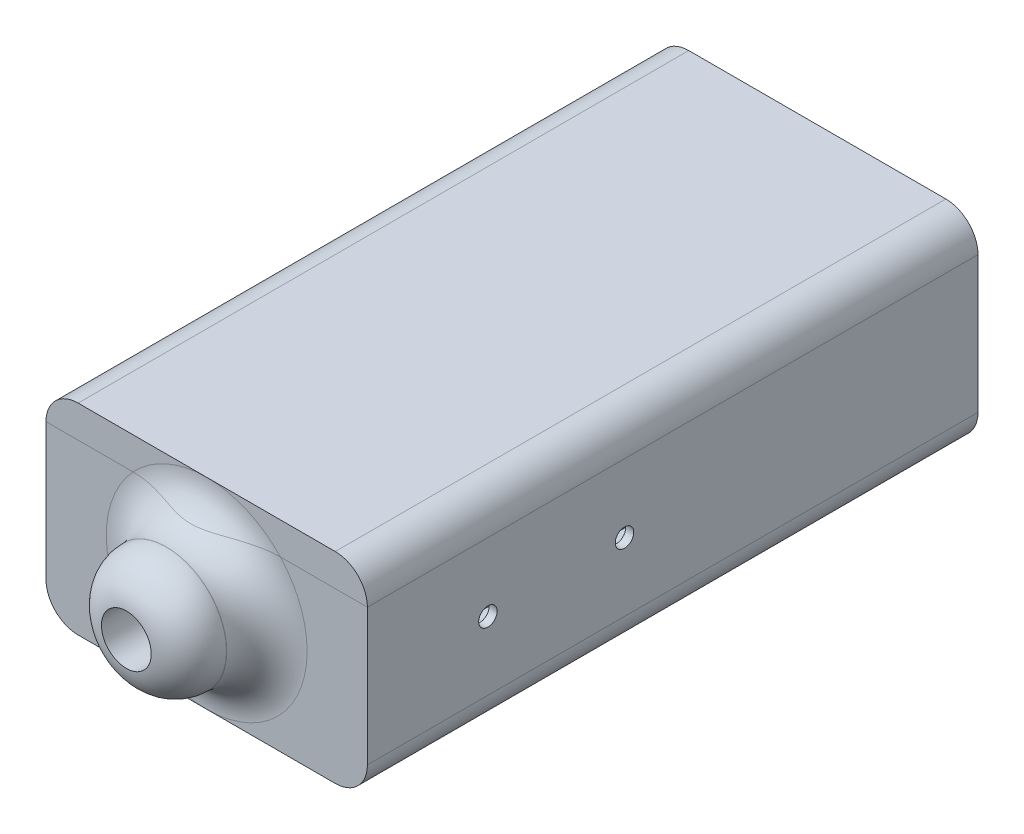
SolidWorks part; units mm, degrees
material "PLA Aero Bambu"
ref_plane "Front Plane" through (0, 0, 0) normal (0, 0, 1) x (1, 0, 0)
ref_plane "Top Plane" through (0, 0, 0) normal (0, 1, 0) x (1, 0, 0)
ref_plane "Right Plane" through (0, 0, 0) normal (1, 0, 0) x (0, 0, -1)
sketch "Sketch1" plane through (0, 0, 0) normal (0, 0, 1) x (1, 0, 0)
  line L1 (-20, 12.5) -> (20, 12.5)
  line L2 (-20, 12.5) -> (-20, -12.5)
  line L3 (-20, -12.5) -> (20, -12.5)
  line L4 (20, 12.5) -> (20, -12.5)
  line L5 (-20, 12.5) -> (20, -12.5) construction
  line L6 (-20, -12.5) -> (20, 12.5) construction
  circle A0 centre (0, 0) radius 2
  point P0 (0, 0)
  dimension "D3" = 4
  dimension "D1" = 25
  dimension "D2" = 40
extrude "Boss-Extrude1" add sketch "Sketch1" against normal blind 1
sketch "Sketch2" plane through (0, 0, -1) normal (0, 0, -1) x (-1, 0, 0)
  line L0 (-20, 12.5) -> (-20, -12.5)
  line L1 (20, -12.5) -> (-20, -12.5) construction
  line L2 (-20, -12.5) -> (20, -12.5)
  line L3 (20, -12.5) -> (20, 12.5)
  line L4 (20, 12.5) -> (-20, 12.5)
  line L5 (19, 11.5) -> (-19, 11.5)
  line L6 (-19, 11.5) -> (-19, -11.5)
  line L7 (-19, -11.5) -> (19, -11.5)
  line L8 (19, -11.5) -> (19, 11.5)
  dimension "D1" = 1
extrude "Boss-Extrude2" add sketch "Sketch2" along normal blind 75
fillet "Fillet2" radius 4 8 edges at (20, 12.5, -38) (20, -12.5, -38) (-20, -12.5, -38) (-20, 12.5, -38) (-19, -11.5, -38.5) (-19, 11.5, -38.5) (19, 11.5, -38.5) (19, -11.5, -38.5)
sketch "Sketch4" plane through (0, 0, 0) normal (0, 0, 1) x (1, 0, 0)
  circle A0 centre (0, 0) radius 7.5
  circle A1 centre (0, 0) radius 3.1
  dimension "D1" = 6.2
  dimension "D2" = 15
extrude "Boss-Extrude3" add sketch "Sketch4" along normal blind 10
fillet "Fillet3" radius 5 2 edges at (7.5, 0, 0) (7.5, 0, 10)
sketch "Sketch5" plane through (20, 0, 0) normal (1, 0, 0) x (0, 0, -1)
  circle A0 centre (15, 0) radius 1.15
  circle A1 centre (32, 0) radius 1.15
  dimension "D1" = 2.3
  dimension "D3" = 2.3
  dimension "D2" = 15
  dimension "D4" = 17
extrude "Cut-Extrude1" cut sketch "Sketch5" against normal through all
sketch "Sketch10" plane through (0, -11.5, 0) normal (0, 1, 0) x (1, 0, 0)
  line L0 (-20, 32.5) -> (20, 32.5)
  line L1 (15, 1) -> (-15, 1) construction
  line L2 (20, 30.85) -> (20, 33.15) construction
  line L3 (-15, 76) -> (-15, 1) construction
  line L5 (-20, 33.15) -> (-20, 30.85) construction
  line L6 (-15, 47.6018) -> (7.4768, 47.6018)
  line L7 (-15, 47.6018) -> (-15, 25.1)
  line L8 (-15, 25.1) -> (7.4768, 25.1)
  line L9 (7.4768, 47.6018) -> (7.4768, 25.1)
  point P2 (13.2446, 32.5)
  line B0 (7.4768, 39.9) -> (13.2446, 39.9) construction
  line B1 (-15, 47.6018) -> (7.4768, 47.6018) construction
  line B2 (-15, 47.6018) -> (-15, 25.1) construction
  line B3 (-15, 25.1) -> (7.4768, 25.1) construction
  line B4 (7.4768, 47.6018) -> (7.4768, 25.1) construction
  line B5 (13.2446, 39.9) -> (13.2446, 25.1) construction
  line B6 (13.2446, 25.1) -> (7.4768, 25.1) construction
  line B7 (3.3268, 47.6165) -> (3.3268, 52.475) construction
  line B8 (3.3268, 52.475) -> (5.8268, 52.475) construction
  line B9 (5.8268, 52.475) -> (5.7933, 47.65) construction
  line B10 (5.8268, 25.1) -> (5.8268, 20.2604) construction
  line B11 (5.8268, 20.2604) -> (3.3268, 20.275) construction
  line B12 (3.3268, 20.275) -> (3.3268, 25.1335) construction
  line M3 (-15, 76) -> (-15, 1)
  dimension "D1" = 31.5
sketch_block_instance "Block1-1"
sketch_block "Block1"
extrude "Boss-Extrude4" add sketch "Sketch10" along normal blind 6 contours L9 L0 L8 M3 | L9 L6 L0 M3 region at (-3.7616, -11.5, -40.0509) region at (-3.7616, -11.5, -28.8)
sketch "Sketch12" plane through (0, -11.5, 0) normal (0, 1, 0) x (1, 0, 0)
  line L0 (3.3268, 52.475) -> (5.8268, 52.475) construction
  line L1 (3.3268, 47.6165) -> (0.8268, 47.6165)
  line L2 (3.3268, 47.6165) -> (3.3268, 52.475)
  line L3 (3.3268, 52.475) -> (0.8268, 52.475)
  line L4 (0.8268, 47.6165) -> (0.8268, 52.475)
  line L6 (3.3268, 25.1335) -> (0.8268, 25.1335)
  line L7 (3.3268, 25.1335) -> (3.3268, 20.275)
  line L8 (3.3268, 20.275) -> (0.8268, 20.2896)
  line L9 (0.8268, 25.1335) -> (0.8268, 20.2896)
  line L11 (5.8268, 20.2604) -> (3.3268, 20.275) construction
  point P5 (2.0768, 52.475)
  dimension "D1" = 0
  dimension "D2" = 2.5
  dimension "D3" = 2.5
extrude "Boss-Extrude5" add sketch "Sketch12" along normal blind 15
sketch "Sketch13" plane through (3.3268, 0, 0) normal (1, 0, 0) x (0, 0, -1)
  line L0 (47.6018, -5.5) -> (25.1, -5.5) construction
  line L1 (20.275, 3.5) -> (25.1335, 3.5) construction
  line L2 (47.6165, 3.5) -> (52.475, 3.5) construction
  circle A0 centre (22.7042, 0) radius 1.35
  circle A1 centre (50.0458, 0) radius 1.35
  point P7 (50.0458, 3.5)
  point P11 (22.7042, 3.5)
  dimension "D2" = 2.7
  dimension "D3" = 2.7
  dimension "D1" = 5.5
extrude "Cut-Extrude3" cut sketch "Sketch13" against normal blind 12
sketch "Sketch15" plane through (0, -11.5, 0) normal (0, 1, 0) x (1, 0, 0)
  line L0 (19, 76) -> (19, 1) construction
  line L1 (9, 18) -> (14, 18)
  line L2 (9, 18) -> (9, 12)
  line L3 (9, 12) -> (14, 12)
  line L4 (14, 18) -> (14, 12)
  line L5 (9, 12) -> (14, 18) construction
  line L6 (14, 12) -> (9, 18) construction
  line L8 (15, 1) -> (-15, 1) construction
  point P6 (11.5, 15)
  dimension "D1" = 5
  dimension "D2" = 6
  dimension "D3" = 5
  dimension "D4" = 14
extrude "Boss-Extrude6" add sketch "Sketch15" along normal blind 14
sketch "Sketch16" plane through (14, 0, 0) normal (1, 0, 0) x (0, 0, -1)
  circle A0 centre (15, 0) radius 1.25
extrude "Cut-Extrude4" cut sketch "Sketch16" against normal blind 5
sketch "Sketch17" plane through (0, 0, -76) normal (0, 0, -1) x (-1, 0, 0)
  line L0 (20, 8.5) -> (-20, 8.5)
split "Split1" trim tools "Sketch17" bodies to split 114 resulting bodies 115 116
